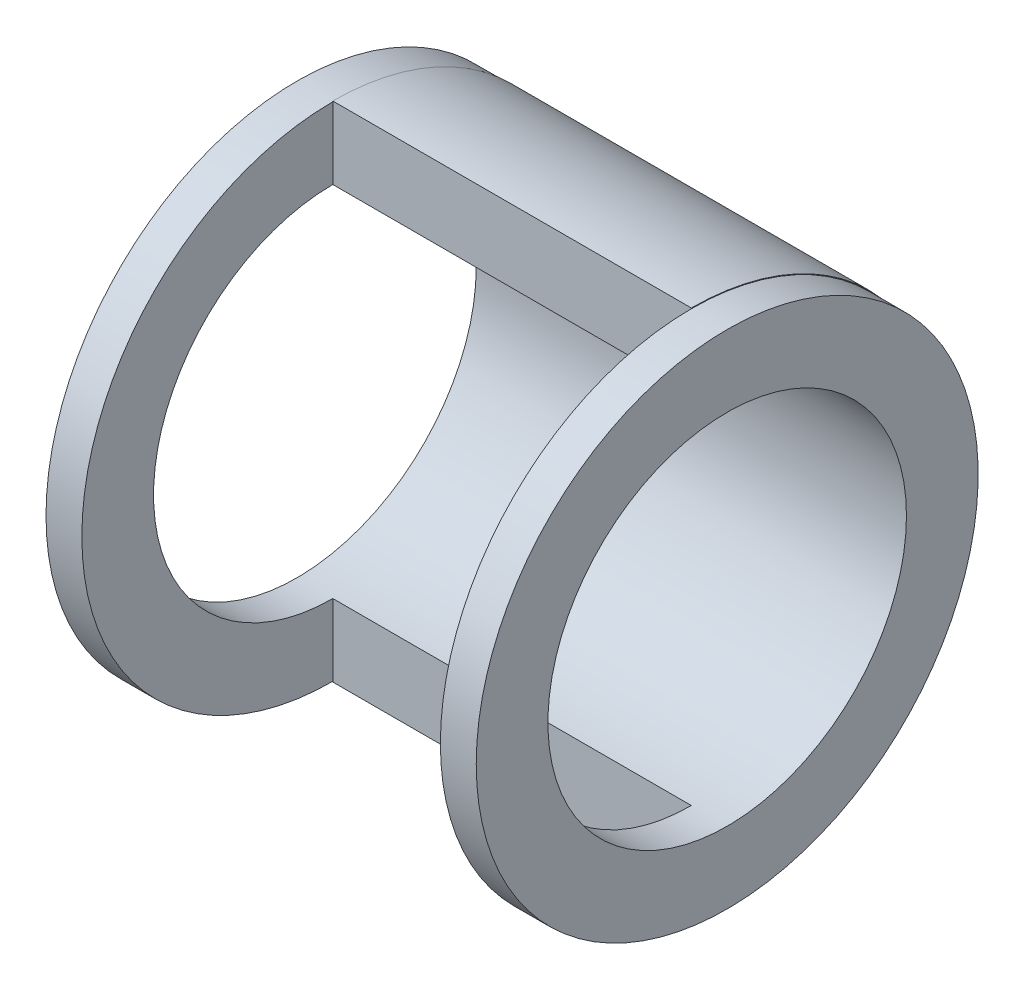
SolidWorks part; units mm, degrees
note: The reader was unsure of these and kept them because the rebuilt part matched: shared geometry of "Esquisse1<4>".
ref_plane "Plan de face" through (0, 0, 0) normal (0, 0, 1) x (1, 0, 0)
ref_plane "Plan de dessus" through (0, 0, 0) normal (0, 1, 0) x (1, 0, 0)
ref_plane "Plan de droite" through (0, 0, 0) normal (1, 0, 0) x (0, 0, -1)
sketch "Esquisse1" plane through (0, 0, 0) normal (0, 0, 1) x (1, 0, 0)
  line L0 (-50, 0) -> (-50, 70)
  line L1 (60, 0) -> (60, 70)
  line L2 (-50, 0) -> (60, 0) construction
  dimension "D1" = 110
  dimension "D2" = 50
  dimension "D3" = 70
  dimension "D4" = 70
revolve "Révol.-Mince2" add sketch "Esquisse1" angle 360 about L2
revolve "Révol.-Mince3" add sketch "Esquisse1<4>" angle 360 about L2
sketch "Esquisse1<4>" plane through (0, 0, 0) normal (0, 0, 1) x (1, 0, 0) same geometry as "Esquisse1"
sketch "Esquisse14" plane through (0, 0, 0) normal (0, 0, 1) x (1, 0, 0)
  line L0 (60, 0) -> (-40, 0)
  line L1 (60, 0) -> (60, 70.1821)
  line L2 (-40, 0) -> (-40, 70.1821)
  line L3 (60, 70.1821) -> (-40, 70.1821)
  line L4 (60, 70) -> (60, -70) construction
  line L5 (-40, -70) -> (-40, 70) construction
revolve "Révolution5" add sketch "Esquisse14" angle 180 about L0
sketch "Esquisse15" plane through (-40, 0, 0) normal (1, 0, 0) x (0, 0, -1)
  line L0 (0, -70) -> (0, 70) construction
  circle A0 centre (0, 0) radius 50
extrude "Enlèv. mat.-Extru.1" cut sketch "Esquisse15" along normal through all both and the other way through all contours A0
sketch "Esquisse13" plane through (60, 0, 0) normal (-1, 0, 0) x (0, 0, 1)
  circle A0 centre (0, 0) radius 50
equation "\"D4@Esquisse1\"=\"D3@Esquisse1\""
